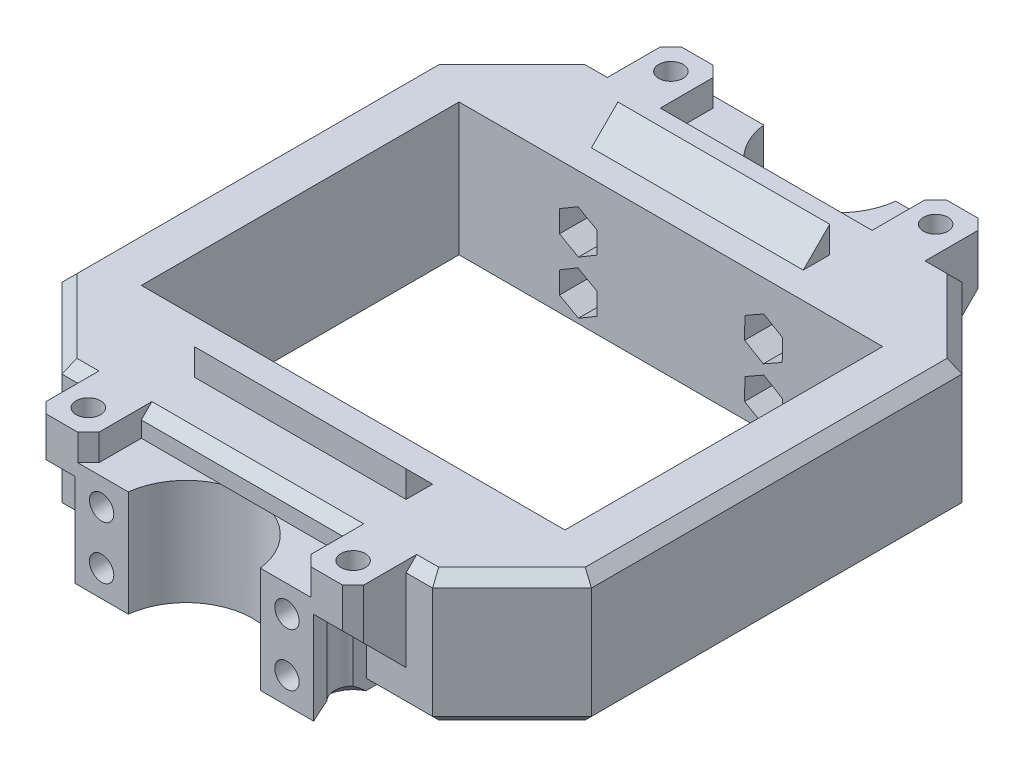
SolidWorks part; units mm, degrees
ref_plane "Front Plane" through (0, 0, 0) normal (0, 0, 1) x (1, 0, 0)
ref_plane "Top Plane" through (0, 0, 0) normal (0, 1, 0) x (1, 0, 0)
ref_plane "Right Plane" through (0, 0, 0) normal (1, 0, 0) x (0, 0, -1)
sketch "Sketch1" plane through (0, 0, 0) normal (0, 1, 0) x (1, 0, 0)
  line L0 (-50, 0) -> (50, 0)
  line L1 (-50, 0) -> (-50, 50)
  line L2 (50, 0) -> (50, 50)
  line L3 (-50, 50) -> (50, 50)
  point P4 (0, 0)
extrude "Boss-Extrude1" add sketch "Sketch1" along normal blind 25
chamfer "Chamfer1" distance 15 2 edges at (-50, 12.5, 0) (50, 12.5, 0)
ref_plane "Plane1" through (0, 25, 0) normal (0, 1, 0) x (1, 0, 0)
sketch "Sketch2" plane through (0, 25, 0) normal (0, 1, 0) x (1, 0, 0)
  line L0 (0, 0) -> (0, 20) construction
  line L1 (-40, 20) -> (40, 20)
  line L2 (-40, 20) -> (-50, 20) construction
  line L4 (-50, 50) -> (-50, 15) construction
  line L5 (40, 20) -> (50, 20) construction
  line L6 (50, 15) -> (50, 50) construction
  line L7 (-40, 20) -> (-40, 50)
  line L8 (50, 50) -> (-50, 50) construction
  line L9 (40, 20) -> (40, 50)
  line L10 (40, 50) -> (-40, 50)
  point P6 (0, 20)
  dimension "D1" = 20
  dimension "D2" = 10
extrude "Cut-Extrude1" cut sketch "Sketch2" against normal up to next
sketch "Sketch3" plane through (0, 25, 0) normal (0, 1, 0) x (1, 0, 0)
  line L0 (-20, 0) -> (20, 0) construction
  line L1 (-35, 0) -> (35, 0) construction
  line L2 (20, 0) -> (20, -10)
  line L3 (20, -10) -> (30, -10)
  line L4 (30, -10) -> (30, 0)
  line L5 (30, 0) -> (20, 0)
  line L6 (-20, 0) -> (-20, -10)
  line L7 (-20, -10) -> (-30, -10)
  line L8 (-30, -10) -> (-30, 0)
  line L9 (-30, 0) -> (-20, 0)
  circle A0 centre (-25, -5) radius 2.3
  circle A1 centre (25, -5) radius 2.3
  point P6 (0, 0)
  dimension "D5" = 4.6
  dimension "D6" = 4.6
  dimension "D1" = 10
  dimension "D2" = 10
  dimension "D3" = 40
  dimension "D4" = 10
extrude "Boss-Extrude2" add sketch "Sketch3" against normal blind 7.5
ref_plane "Plane2" through (0, 0, 10) normal (0, 0, 1) x (1, 0, 0)
chamfer "Chamfer3" distance 10 2 edges at (25, 17.5, 0) (-25, 17.5, 0)
sketch "Sketch5" plane through (0, 25, 0) normal (0, 1, 0) x (1, 0, 0)
  circle A0 centre (-25, -5) radius 3.5
  circle A1 centre (25, -5) radius 3.5
  dimension "D1" = 7
  dimension "D2" = 7
extrude "Cut-Extrude3" cut sketch "Sketch5" against normal up to next from offset 6 offset against normal yes
sketch "Sketch6" plane through (0, 25, 0) normal (0, 1, 0) x (1, 0, 0)
  line L0 (-20, 0) -> (-20, 10) construction
  line L1 (-20, 10) -> (20, 10)
  line L2 (20, 10) -> (20, 15)
  line L3 (20, 15) -> (-20, 15)
  line L4 (-20, 15) -> (-20, 10)
  dimension "D1" = 10
  dimension "D2" = 40
  dimension "D3" = 5
extrude "Boss-Extrude4" add sketch "Sketch6" along normal blind 5
chamfer "Chamfer4" distance 5 1 edges at (0, 30, -15)
extrude "Cut-Extrude4" cut sketch "Sketch6<2>" along normal blind 5 from surface starting at face at (0, 0, -27)
sketch "Sketch6<2>" plane through (0, 25, 0) normal (0, 1, 0) x (1, 0, 0) same geometry as "Sketch6"
chamfer "Chamfer5" distance 4.75 1 edges at (0, 5, -15)
ref_plane "Plane3" through (0, 0, -50) normal (0, 0, -1) x (-1, 0, 0)
sketch "Sketch7" plane through (0, 0, -50) normal (0, 0, -1) x (-1, 0, 0)
  line L0 (45, 0) -> (45, 5) construction
  line L1 (40, 0) -> (50, 0) construction
  line L2 (45, 25) -> (45, 20) construction
  line L3 (40, 25) -> (50, 25) construction
  line L4 (47.5, 5) -> (42.5, 5)
  line L5 (42.5, 5) -> (42.5, 10)
  line L6 (42.5, 10) -> (47.5, 10)
  line L7 (47.5, 10) -> (47.5, 5)
  line L8 (47.5, 20) -> (42.5, 20)
  line L9 (42.5, 20) -> (42.5, 15)
  line L10 (42.5, 15) -> (47.5, 15)
  line L11 (47.5, 15) -> (47.5, 20)
  point P11 (45, 5)
  point P16 (45, 20)
  dimension "D2" = 5
  dimension "D4" = 5
  dimension "D1" = 5
  dimension "D3" = 5
  dimension "D5" = 5
  dimension "D6" = 5
sketch "Sketch8" plane through (0, 0, -50) normal (0, 0, -1) x (-1, 0, 0)
  line L0 (-45, 25) -> (-45, 20) construction
  line L1 (-50, 25) -> (-40, 25) construction
  line L2 (-45, 0) -> (-45, 5) construction
  line L3 (-50, 0) -> (-40, 0) construction
  line L4 (-47.5, 20) -> (-42.5, 20)
  line L5 (-42.5, 20) -> (-42.5, 15)
  line L6 (-42.5, 15) -> (-47.5, 15)
  line L7 (-47.5, 15) -> (-47.5, 20)
  line L8 (-47.5, 5) -> (-42.5, 5)
  line L9 (-42.5, 5) -> (-42.5, 10)
  line L10 (-42.5, 10) -> (-47.5, 10)
  line L11 (-47.5, 10) -> (-47.5, 5)
  point P11 (-45, 20)
  point P16 (-45, 5)
  dimension "D3" = 5
  dimension "D4" = 5
  dimension "D1" = 5
  dimension "D2" = 5
  dimension "D5" = 5
  dimension "D6" = 5
sketch "Sketch9" plane through (0, 0, 10) normal (0, 0, 1) x (1, 0, 0)
  line L0 (-22.5, 0) -> (22.5, 0)
  line L2 (-22.5, 0) -> (-22.5, 20)
  line L4 (-22.5, 20) -> (22.5, 20)
  line L6 (22.5, 20) -> (22.5, 0)
  point P6 (0, 0)
  point P12 (-20, 0)
  dimension "D1" = 20
  dimension "D2" = 45
extrude "Boss-Extrude5" add sketch "Sketch9" against normal blind 10
extrude "Cut-Extrude5" cut sketch "Sketch5<2>" against normal up to next
sketch "Sketch5<2>" plane through (0, 25, 0) normal (0, 1, 0) x (1, 0, 0) same geometry as "Sketch5"
sketch "Sketch10" plane through (0, 25, 0) normal (0, 1, 0) x (1, 0, 0)
  line L0 (20, -10) -> (-20, -10) construction
  line L1 (0, -10) -> (0, -11.5) construction
  circle A0 centre (0, -11.5) radius 12.55
  dimension "D2" = 25.1
  dimension "D1" = 1.5
extrude "Cut-Extrude6" cut sketch "Sketch10" along normal blind 20 from surface starting at face at (0, 0, -12.7778)
ref_plane "Plane4" through (0, 0, 10) normal (0, 0, 1) x (1, 0, 0)
sketch "Sketch11" plane through (0, 0, 10) normal (0, 0, 1) x (1, 0, 0)
  line L0 (-17.5, 10) -> (0, 10) construction
  line L2 (-17.5, 5) -> (-17.5, 15) construction
  line L3 (0, 0) -> (0, 10) construction
  circle A0 centre (-17.5, 15) radius 2.3
  circle A1 centre (-17.5, 5) radius 2.3
  point P7 (-17.5, 10)
  dimension "D3" = 4.6
  dimension "D4" = 4.6
  dimension "D1" = 17.5
  dimension "D2" = 10
extrude "Cut-Extrude7" cut sketch "Sketch11" against normal up to next
mirror "Mirror1" about plane through (0, 0, 0) normal (1, 0, 0) of "Cut-Extrude7"
sketch "Sketch12" plane through (0, 0, 10) normal (0, 0, 1) x (1, 0, 0)
  line L1 (-17.46, 10.901) -> (-13.9302, 12.9851)
  line L2 (-13.9302, 12.9851) -> (-13.9701, 17.0841)
  line L3 (-13.9701, 17.0841) -> (-17.54, 19.099)
  line L4 (-17.54, 19.099) -> (-21.0698, 17.0149)
  line L5 (-21.0698, 17.0149) -> (-21.0299, 12.9159)
  line L6 (-21.0299, 12.9159) -> (-17.46, 10.901)
  line L7 (-17.46, 0.901) -> (-13.9302, 2.9851)
  line L8 (-13.9302, 2.9851) -> (-13.9701, 7.0841)
  line L9 (-13.9701, 7.0841) -> (-17.54, 9.099)
  line L10 (-17.54, 9.099) -> (-21.0698, 7.0149)
  line L11 (-21.0698, 7.0149) -> (-21.0299, 2.9159)
  line L12 (-21.0299, 2.9159) -> (-17.46, 0.901)
  circle A0 centre (-17.5, 15) radius 3.55 construction
  circle A1 centre (-17.5, 5) radius 3.55 construction
  dimension "D1" = 7.1
  dimension "D2" = 7.1
extrude "Cut-Extrude8" cut sketch "Sketch12" against normal up to next from offset 10 offset against normal yes
mirror "Mirror2" about plane through (0, 0, 0) normal (1, 0, 0) of "Cut-Extrude8"
mirror "Mirror4" about plane through (0, 0, -50) normal (0, 0, -1) of bodies 120
chamfer "Chamfer6" distance 2 35 edges at (21.5, 0, 5) (20, 22.5, 10) (-30, 21.25, 10) (-21.5, 0, 5) (-28.75, 0, 0) (-42.5, 0, -7.5) (-50, 0, -50) (-28.75, 0, -100) (-42.5, 0, -92.5) (-21.5, 0, -105) (-20, 22.5, -110) (-30, 21.25, -110) (-32.5, 25, -100) (-32.5, 25, 0) (-42.5, 25, -7.5) (-50, 25, -50) (-42.5, 25, -92.5) (0, 25, -100) (0, 25, 0) (-20, 22.5, 10) (30, 21.25, 10) (21.5, 0, -105) (22.5, 0, -108.7247) (28.75, 0, 0) (42.5, 0, -7.5) (28.75, 0, -100) (42.5, 0, -92.5) (50, 0, -50) (20, 22.5, -110) (30, 21.25, -110) (32.5, 25, 0) (42.5, 25, -7.5) (32.5, 25, -100) (42.5, 25, -92.5) (50, 25, -50)
extrude "Extrude-Thin1" add sketch "Sketch5<3>" against normal blind 6 thin thin type one direction reverse wall 1.2
sketch "Sketch5<3>" plane through (0, 25, 0) normal (0, 1, 0) x (1, 0, 0) same geometry as "Sketch5"
mirror "Mirror5" about plane through (0, 0, -50) normal (0, 0, -1) of "Extrude-Thin1"
